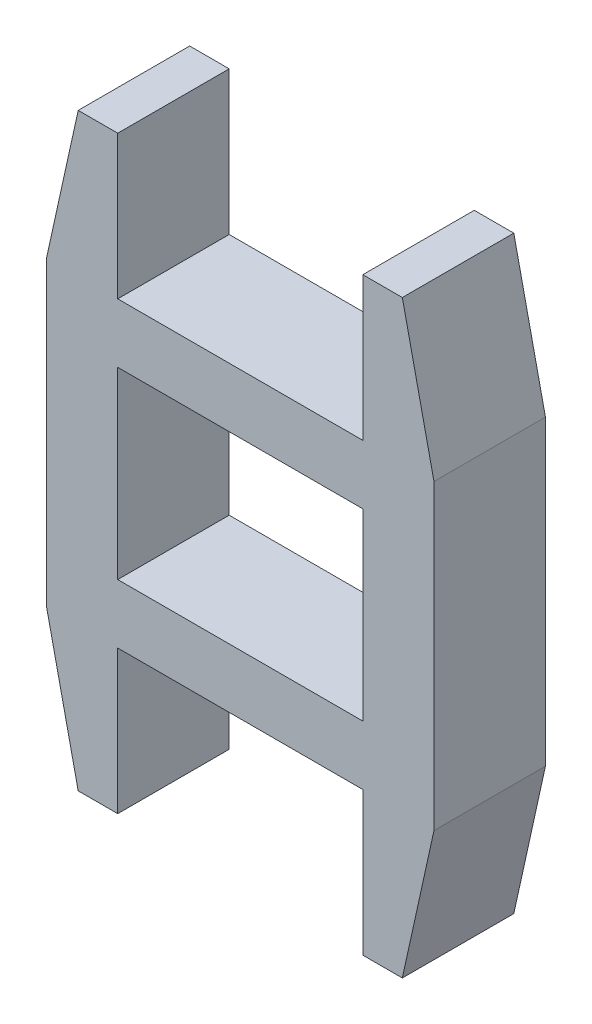
SolidWorks part; units mm, degrees
material "Acrylic (Medium-high impact)"
ref_plane "Front Plane" through (0, 0, 0) normal (0, 0, 1) x (1, 0, 0)
ref_plane "Top Plane" through (0, 0, 0) normal (0, 1, 0) x (1, 0, 0)
ref_plane "Right Plane" through (0, 0, 0) normal (1, 0, 0) x (0, 0, -1)
sketch "Sketch1" plane through (0, 0, 0) normal (0, 0, 1) x (1, 0, 0)
  line L0 (1247.2096, 960.5272) -> (1247.2096, 951.2272)
  line L1 (1263.2096, 949.7272) -> (1243.6096, 949.7272) construction
  line L2 (1247.2096, 948.2272) -> (1243.6096, 948.2272) construction
  line L3 (1247.2096, 960.5272) -> (1259.6096, 960.5272)
  line L4 (1245.2096, 970.7864) -> (1247.2096, 970.7864)
  line L5 (1247.2096, 970.7864) -> (1247.2096, 963.5272)
  line L6 (1247.2096, 955.8772) -> (1259.6096, 955.8772) construction
  line L7 (1259.6096, 963.5272) -> (1247.2096, 963.5272)
  line L8 (1243.6096, 963.5272) -> (1243.6096, 948.2272)
  line L9 (1243.6096, 948.2272) -> (1245.2096, 940.968)
  line L10 (1247.2096, 963.5272) -> (1243.6096, 963.5272) construction
  line L11 (1259.6096, 948.2272) -> (1247.2096, 948.2272)
  line L12 (1243.6096, 963.5272) -> (1245.2096, 970.7864)
  line L13 (1247.2096, 940.968) -> (1247.2096, 948.2272)
  line L14 (1245.2096, 940.968) -> (1247.2096, 940.968)
  line L15 (1247.2096, 951.2272) -> (1259.6096, 951.2272)
  line L16 (1259.6096, 963.5272) -> (1263.2096, 963.5272) construction
  line L17 (1259.6096, 948.2272) -> (1263.2096, 948.2272) construction
  line L18 (1261.6096, 940.968) -> (1259.6096, 940.968)
  line L19 (1253.4096, -37.9351) -> (1253.4096, 49962.0649) construction
  line L20 (1259.6096, 940.968) -> (1259.6096, 948.2272)
  line L21 (1263.2096, 963.5272) -> (1261.6096, 970.7864)
  line L22 (1263.2096, 948.2272) -> (1261.6096, 940.968)
  line L23 (1263.2096, 963.5272) -> (1263.2096, 948.2272)
  line L24 (1259.6096, 970.7864) -> (1259.6096, 963.5272)
  line L25 (1261.6096, 970.7864) -> (1259.6096, 970.7864)
  line L26 (1263.2096, 962.0272) -> (1243.6096, 962.0272) construction
  line L27 (1259.6096, 960.5272) -> (1259.6096, 951.2272)
  point P2 (1263.2096, 955.8772)
  point P14 (1243.6096, 955.8772)
  point P15 (1253.4096, 963.5272)
  point P20 (1253.4096, 962.0272)
  point P26 (1253.4096, 955.8772)
  point P28 (1253.4096, 963.5272)
  point P30 (1253.4096, 960.5272)
  point P31 (1253.4096, 949.7272)
  point P33 (1253.4096, 951.2272)
  point P36 (1253.4096, 948.2272)
  point P38 (1253.4096, 960.5272)
  dimension "D1" = 6.2
  dimension "D2" = 7.2592
  dimension "D3" = 2
  dimension "D4" = 3
  dimension "D8" = 3.6
extrude "Boss-Extrude1" add sketch "Sketch1" along normal blind 5.64
